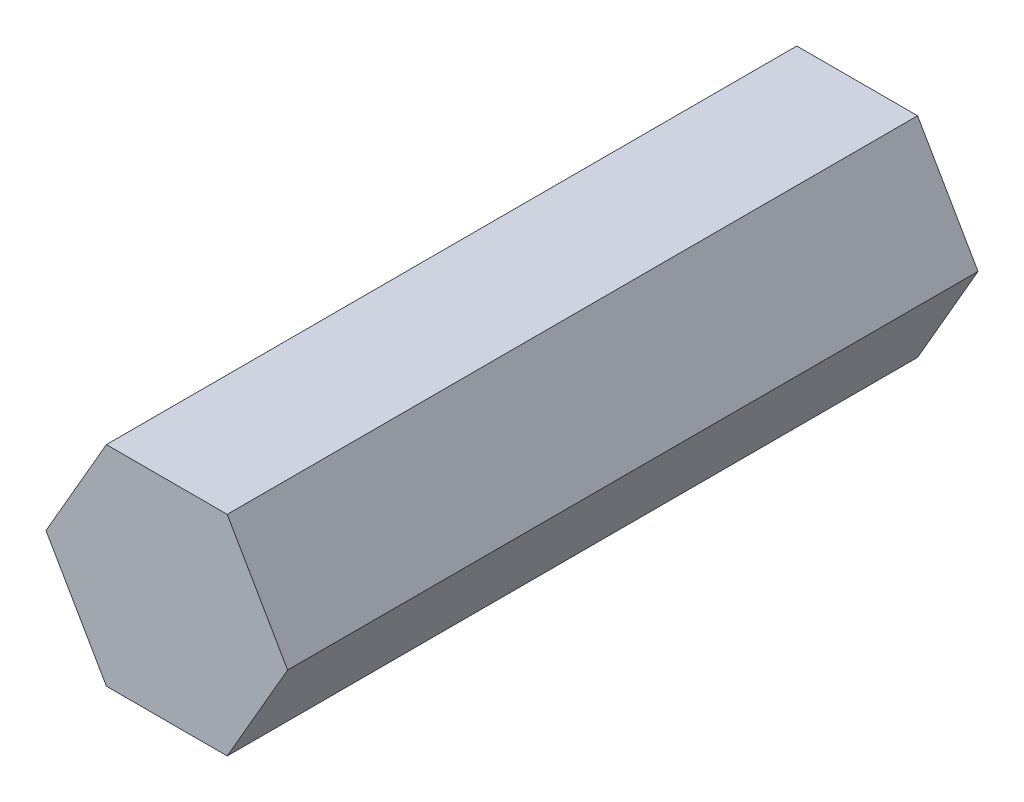
SolidWorks part; units mm, degrees
ref_plane "정면" through (0, 0, 0) normal (0, 0, 1) x (1, 0, 0)
ref_plane "윗면" through (0, 0, 0) normal (0, 1, 0) x (1, 0, 0)
ref_plane "우측면" through (0, 0, 0) normal (1, 0, 0) x (0, 0, -1)
ref_axis "기준축2" through (0, 0, 210) along (0, 0, -1)
ref_axis "기준축4" through (0, 55, 0) along (0, -1, 0)
sketch "스케치1" plane through (0, 0, 0) normal (0, 0, 1) x (1, 0, 0)
  line L1 (35, 0) -> (17.5, 30.3109)
  line L2 (17.5, 30.3109) -> (-17.5, 30.3109)
  line L3 (-17.5, 30.3109) -> (-35, 0)
  line L4 (-35, 0) -> (-17.5, -30.3109)
  line L5 (-17.5, -30.3109) -> (17.5, -30.3109)
  line L6 (17.5, -30.3109) -> (35, 0)
  circle A0 centre (0, 0) radius 35 construction
  dimension "D1" = 70
extrude "보스-돌출1" add sketch "스케치1" along normal blind 200
